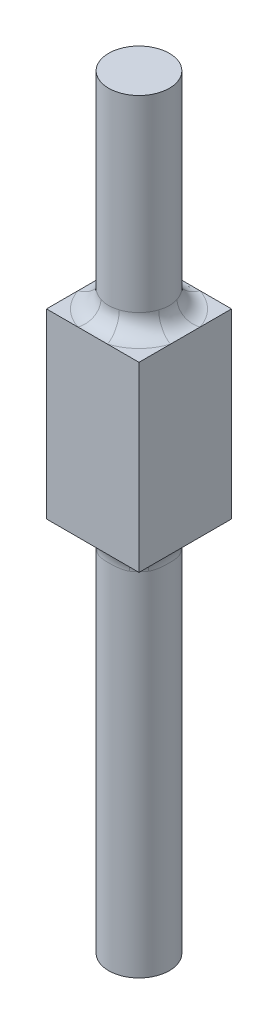
SolidWorks part; units mm, degrees
ref_plane "Front Plane" through (0, 0, 0) normal (0, 0, 1) x (1, 0, 0)
ref_plane "Top Plane" through (0, 0, 0) normal (0, 1, 0) x (1, 0, 0)
ref_plane "Right Plane" through (0, 0, 0) normal (1, 0, 0) x (0, 0, -1)
sketch "Sketch1" plane through (0, 0, 0) normal (0, 1, 0) x (1, 0, 0)
  circle A0 centre (0, 0) radius 5
  dimension "D1" = 10
extrude "Boss-Extrude1" add sketch "Sketch1" along normal blind 62
sketch "Sketch3" plane through (0, 62, 0) normal (0, 1, 0) x (1, 0, 0)
  line L1 (-7.625, -7.625) -> (7.625, -7.625)
  line L2 (-7.625, -7.625) -> (-7.625, 7.625)
  line L3 (-7.625, 7.625) -> (7.625, 7.625)
  line L4 (7.625, -7.625) -> (7.625, 7.625)
  line L5 (-7.625, -7.625) -> (7.625, 7.625) construction
  line L6 (-7.625, 7.625) -> (7.625, -7.625) construction
  point P0 (0, 0)
  dimension "D1" = 15.25
  dimension "D2" = 15.25
extrude "Boss-Extrude2" add sketch "Sketch3" along normal blind 30
sketch "Sketch4" plane through (0, 92, 0) normal (0, 1, 0) x (1, 0, 0)
  circle A0 centre (0, 0) radius 5
  dimension "D1" = 10
sketch "Sketch5" plane through (0, 0, 0) normal (0, -1, 0) x (1, 0, 0)
  circle A0 centre (0, 0) radius 3
  dimension "D1" = 6
extrude "Cut-Extrude1" cut sketch "Sketch5" against normal blind 10
fillet "Fillet1" radius 4 1 edges at (0, 62, 5)
extrude "Boss-Extrude3" add sketch "Sketch4" along normal blind 34
fillet "Fillet2" radius 3 1 edges at (0, 92, 5)
